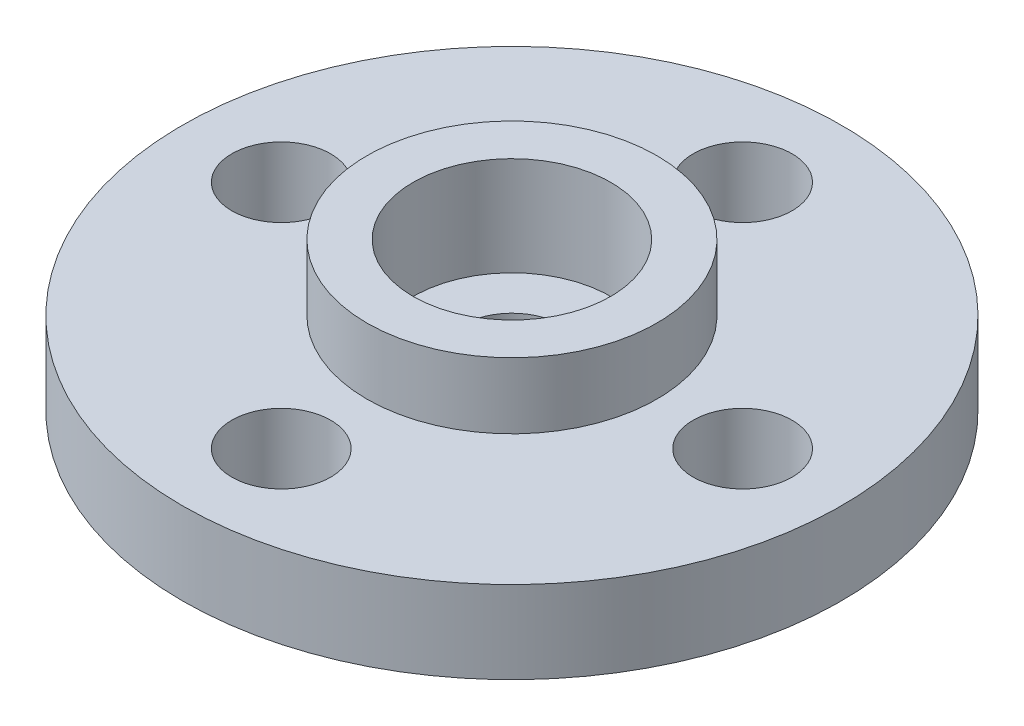
SolidWorks part; units mm, degrees
ref_plane "前视基准面" through (0, 0, 0) normal (0, 0, 1) x (1, 0, 0)
ref_plane "上视基准面" through (0, 0, 0) normal (0, 1, 0) x (1, 0, 0)
ref_plane "右视基准面" through (0, 0, 0) normal (1, 0, 0) x (0, 0, -1)
sketch "草图4" plane through (0, 0, 0) normal (0, 1, 0) x (1, 0, 0)
  circle A0 centre (0, 0) radius 10
  dimension "D1" = 20
extrude "凸台-拉伸2" add sketch "草图4" along normal blind 2.5
ref_plane "基准面7" through (0, 2.5, 0) normal (0, 1, 0) x (1, 0, 0)
sketch "草图6" plane through (0, 2.5, 0) normal (0, 1, 0) x (1, 0, 0)
  circle A0 centre (0, 0) radius 7 construction
  circle A1 centre (0, 7) radius 1.5
  circle A2 centre (0, 0) radius 1.5
  circle A3 centre (7, 0) radius 1.5
  circle A4 centre (-7, 0) radius 1.5
  circle A5 centre (0, -7) radius 1.5
  dimension "D1" = 3
  dimension "D2" = 3
  dimension "D3" = 3
  dimension "D4" = 3
  dimension "D5" = 3
  dimension "D6" = 14
extrude "切除-拉伸9" cut sketch "草图6" against normal blind 2.5
sketch "草图7" plane through (0, 2.5, 0) normal (0, 1, 0) x (1, 0, 0)
  circle A0 centre (0, 0) radius 4.4
  dimension "D1" = 8.8
extrude "凸台-拉伸3" add sketch "草图7" along normal blind 2
ref_plane "基准面8" through (0, 4.5, 0) normal (0, 1, 0) x (1, 0, 0)
sketch "草图8" plane through (0, 4.5, 0) normal (0, 1, 0) x (1, 0, 0)
  circle A0 centre (0, 0) radius 3
  dimension "D1" = 6
extrude "切除-拉伸10" cut sketch "草图8" against normal blind 3
ref_axis "基准轴1" through (0, 1.5, 0) along (0, 1, 0)
